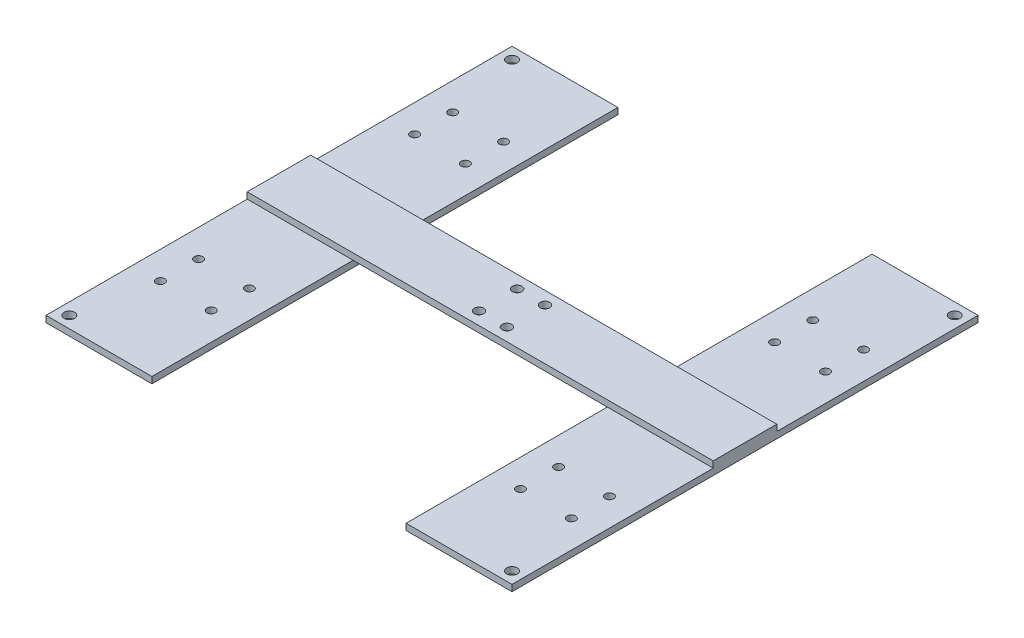
SolidWorks part; units mm, degrees
note: The reader was unsure of these and kept them because the rebuilt part matched: shared geometry of "Sketch1<4>".
material "1060 Alloy"
ref_plane "Front Plane" through (0, 0, 0) normal (0, 0, 1) x (1, 0, 0)
ref_plane "Top Plane" through (0, 0, 0) normal (0, 1, 0) x (1, 0, 0)
ref_plane "Right Plane" through (0, 0, 0) normal (1, 0, 0) x (0, 0, -1)
sketch "Sketch1" plane through (0, 0, 0) normal (0, 1, 0) x (1, 0, 0)
  line L0 (0, 114.8866) -> (0, -113.5667) construction
  line L1 (-110, 110) -> (-60, 110)
  line L2 (-110, 110) -> (-110, -110)
  line L3 (-110, -110) -> (-60, -110)
  line L4 (-60, 110) -> (-60, -110)
  line L5 (60, 110) -> (110, 110)
  line L6 (60, 110) -> (60, -110)
  line L7 (60, -110) -> (110, -110)
  line L8 (110, 110) -> (110, -110)
  line L9 (-60, 15) -> (60, 15)
  line L10 (-60, 15) -> (-60, -15)
  line L11 (-60, -15) -> (60, -15)
  line L12 (60, 15) -> (60, -15)
  line L13 (-123.5708, 0) -> (140.9151, 0) construction
  line L15 (-102, 75) -> (-68, 75) construction
  line L16 (-102, 75) -> (-102, 45) construction
  line L17 (-102, 45) -> (-68, 45) construction
  line L18 (-68, 75) -> (-68, 45) construction
  line L30 (-85, 75) -> (-85, 45) construction
  line L31 (-102, 60) -> (-68, 60) construction
  line L32 (102, 60) -> (68, 60) construction
  line L33 (85, 75) -> (85, 45) construction
  line L34 (68, 75) -> (68, 45) construction
  line L35 (102, 45) -> (68, 45) construction
  line L36 (102, 75) -> (102, 45) construction
  line L37 (102, 75) -> (68, 75) construction
  line L38 (102, -75) -> (68, -75) construction
  line L39 (102, -75) -> (102, -45) construction
  line L40 (102, -45) -> (68, -45) construction
  line L41 (68, -75) -> (68, -45) construction
  line L42 (85, -75) -> (85, -45) construction
  line L43 (102, -60) -> (68, -60) construction
  line L44 (-102, -60) -> (-68, -60) construction
  line L45 (-85, -75) -> (-85, -45) construction
  line L46 (-68, -75) -> (-68, -45) construction
  line L47 (-102, -45) -> (-68, -45) construction
  line L48 (-102, -75) -> (-102, -45) construction
  line L49 (-102, -75) -> (-68, -75) construction
  line L50 (-60, 15) -> (-110, 15)
  line L51 (-60, -15) -> (-110, -15)
  line L52 (60, -15) -> (110, -15)
  line L53 (60, 15) -> (110, 15)
  circle A0 centre (-97, 69) radius 2
  circle A1 centre (-73, 69) radius 2
  circle A2 centre (-73, 51) radius 2
  circle A3 centre (-97, 51) radius 2
  circle A4 centre (97, 51) radius 2
  circle A5 centre (73, 51) radius 2
  circle A6 centre (73, 69) radius 2
  circle A7 centre (97, 69) radius 2
  circle A8 centre (97, -69) radius 2
  circle A9 centre (73, -69) radius 2
  circle A10 centre (73, -51) radius 2
  circle A11 centre (97, -51) radius 2
  circle A12 centre (-97, -51) radius 2
  circle A13 centre (-73, -51) radius 2
  circle A14 centre (-73, -69) radius 2
  circle A15 centre (-97, -69) radius 2
  circle A16 centre (-104.5, 104.5) radius 2.5
  circle A17 centre (104.5, 104.5) radius 2.5
  circle A18 centre (-104.5, -104.5) radius 2.5
  circle A19 centre (104.5, -104.5) radius 2.5
  circle A20 centre (-6.575, 9) radius 2.25
  circle A21 centre (6.575, 9) radius 2.25
  circle A22 centre (6.575, -9) radius 2.25
  circle A23 centre (-6.575, -9) radius 2.25
  point P16 (0, 0)
  dimension "D6" = 4
  dimension "D12" = 5
  dimension "D15" = 13.15
  dimension "D16" = 4.5
  dimension "D1" = 220
  dimension "D2" = 220
  dimension "D3" = 30
  dimension "D4" = 34
  dimension "D5" = 30
  dimension "D7" = 18
  dimension "D8" = 120
  dimension "D9" = 24
  dimension "D10" = 60
  dimension "D11" = 170
  dimension "D13" = 209
  dimension "D14" = 209
  dimension "D17" = 6
extrude "Boss-Extrude1" add sketch "Sketch1" along normal blind 3 contours L4 L1 L2 L3 A15 A13 A0 A1 A2 A3 A12 A14 A16 A18 | L8 L5 L6 L7 A19 A7 A5 A4 A6 A8 A9 A10 A11 A17 | L4 L51 L2 L3 A15 A13 A12 A14 A18 | L50 L4 L1 L2 A16 A3 A2 A1 A0 | L6 L53 L8 L5 A7 A5 A4 A6 A17 | L52 L6 L7 L8 A19 A11 A10 A9 A8
extrude "Boss-Extrude2" add sketch "Sketch1<4>" along normal blind 3 from surface at 3 contours L4 L11 L6 L9 | L51 L4 L50 L2 | L53 L6 L52 L8
sketch "Sketch1<4>" plane through (0, 0, 0) normal (0, 1, 0) x (1, 0, 0) same geometry as "Sketch1"
